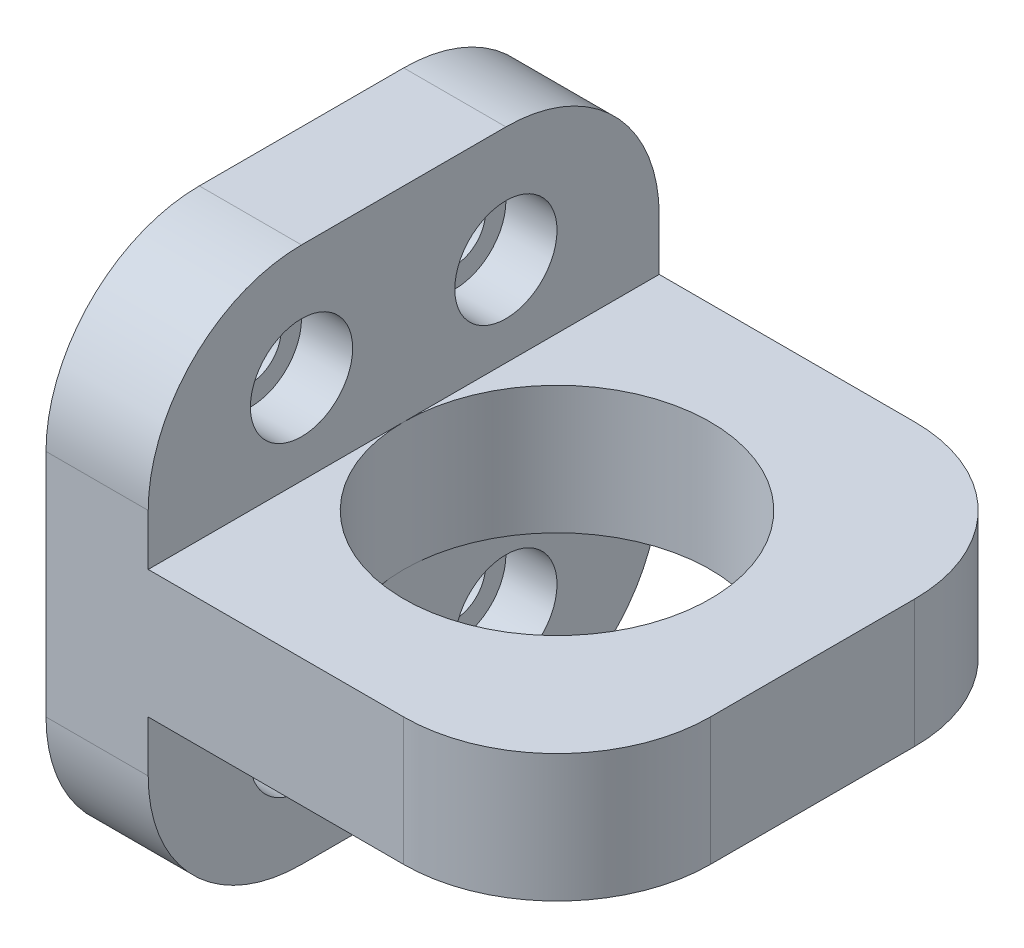
SolidWorks part; units mm, degrees
ref_plane "前视基准面" through (0, 0, 0) normal (0, 0, 1) x (1, 0, 0)
ref_plane "上视基准面" through (0, 0, 0) normal (0, 1, 0) x (1, 0, 0)
ref_plane "右视基准面" through (0, 0, 0) normal (1, 0, 0) x (0, 0, -1)
other "Configuration Table"
sketch "草图1" plane through (0, 0, 0) normal (0, 1, 0) x (1, 0, 0)
  line L13 (-5, -5) -> (5, -5)
  line L14 (-5, -5) -> (-5, 5)
  line L15 (-5, 5) -> (5, 5)
  line L16 (5, -5) -> (5, 5)
  line L17 (-5, -5) -> (5, 5) construction
  line L18 (-5, 5) -> (5, -5) construction
  circle A0 centre (0, 0) radius 3
  dimension "D1" = 10
  dimension "D3" = 6
  dimension "D2" = 10
extrude "凸台-拉伸1" add sketch "草图1" along normal blind 2.5
sketch "草图3" plane through (-5, 0, 0) normal (-1, 0, 0) x (0, 0, 1)
  line L0 (-5, 2.5) -> (-5, 0) construction
  line L1 (5, 6.5) -> (-5, 6.5)
  line L2 (5, 6.5) -> (5, -4)
  line L3 (5, -4) -> (-5, -4)
  line L4 (-5, 6.5) -> (-5, -4)
  line L5 (5, 2.5) -> (5, 0) construction
  line L6 (-5, 0) -> (5, 0) construction
  line L7 (-5, 2.5) -> (5, 2.5) construction
  circle A0 centre (-2, 4.25) radius 1
  circle A1 centre (-2, 4.25) radius 0.6
  circle A2 centre (2, 4.25) radius 0.6
  circle A3 centre (2, 4.25) radius 1
  circle A4 centre (-2, -1.75) radius 0.6
  circle A5 centre (-2, -1.75) radius 1
  circle A6 centre (2, -1.75) radius 0.6
  circle A7 centre (2, -1.75) radius 1
  point P24 (0, 0)
  dimension "D3" = 1.2
  dimension "D4" = 2
  dimension "D1" = 4
  dimension "D2" = 4
extrude "凸台-拉伸2" add sketch "草图3" against normal blind 2 contours L2 L3 L4 L1
extrude "切除-拉伸1" cut sketch "草图3<3>" against normal through all contours A6 | A2 | A1 | A4
sketch "草图3<3>" plane through (-5, 0, 0) normal (-1, 0, 0) x (0, 0, 1) same geometry as "草图3"
extrude "切除-拉伸2" cut sketch "草图3<4>" along normal offset from surface (1 mm away) 1 from surface contours A0 | A3 | A7 | A5 up to face at (-5, -1.75, -1.4) starting at face at (-3, 4.25, -1.4)
sketch "草图3<4>" plane through (-5, 0, 0) normal (-1, 0, 0) x (0, 0, 1) same geometry as "草图3"
fillet "圆角1" radius 3 2 edges at (5, 1.25, -5) (5, 1.25, 5)
fillet "圆角2" radius 3 4 edges at (-4, -4, 5) (-4, -4, -5) (-4, 6.5, -5) (-4, 6.5, 5)
